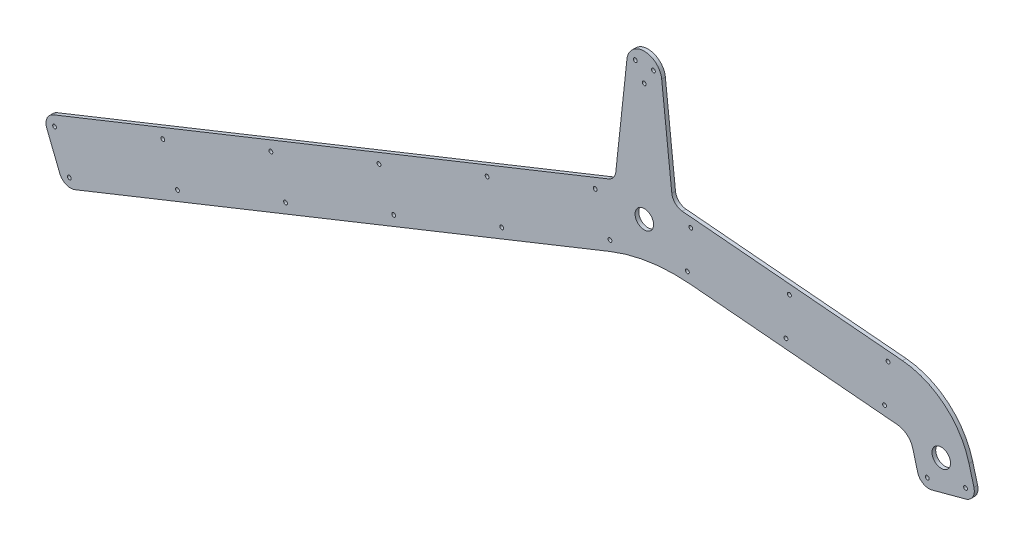
SolidWorks part; units mm, degrees
ref_plane "Front Plane" through (0, 0, 0) normal (0, 0, 1) x (1, 0, 0)
ref_plane "Top Plane" through (0, 0, 0) normal (0, 1, 0) x (1, 0, 0)
ref_plane "Right Plane" through (0, 0, 0) normal (1, 0, 0) x (0, 0, -1)
sketch "Sketch1" plane through (0, 0, 0) normal (0, 0, 1) x (1, 0, 0)
  line L0 (-325, 0) -> (325, 0) construction
  line L1 (-475, -190) -> (-325, 0) construction
  line L2 (325, 0) -> (475, -190) construction
  line L3 (-75, -190) -> (145, -190) construction
  line L4 (145, -190) -> (365, -190) construction
  line L5 (-25.1427, 16.8688) -> (-516.7815, -179.7868)
  line L6 (-516.7815, -179.7868) -> (-498.2119, -226.2106)
  line L7 (-498.2119, -226.2106) -> (-29.4264, -38.6964)
  line L8 (-507.4967, -202.9987) -> (-475, -190) construction
  line L9 (39.3556, -28.5387) -> (217.3643, -44.1124)
  line L11 (221.7221, 5.6973) -> (24.4857, 22.9533)
  line L12 (-25.1427, 16.8688) -> (-6.5731, -29.5551) construction
  line L13 (35, -190) -> (255, -49.8445) construction
  line L14 (255, -49.8445) -> (475, -190) construction
  line L15 (-25.1427, 16.8688) -> (-14.9133, 111.6102)
  line L16 (14.9133, 111.6102) -> (24.4857, 22.9533)
  line L17 (325, 0) -> (325, 80) construction
  line L18 (325, 80) -> (-325, 80) construction
  line L19 (-325, 80) -> (-325, 0) construction
  line L20 (24.4857, 22.9533) -> (20.1279, -26.8565) construction
  line L21 (-15.8579, -6.3432) -> (0, 0) construction
  line L22 (-25.1427, 16.8688) -> (24.4857, 22.9533) construction
  line L23 (230.5459, -55.173) -> (237.3223, -80.4632)
  line L24 (237.3223, -80.4632) -> (285.6186, -67.5222)
  line L25 (285.6186, -67.5222) -> (278.8422, -42.2321)
  line L26 (261.4705, -73.9927) -> (255, -49.8445) construction
  line L29 (0, 0) -> (22.3068, -1.9516) construction
  circle A0 centre (0, 0) radius 7.9375
  circle A1 centre (-475, -190) radius 110 construction
  circle A2 centre (35, -190) radius 110 construction
  circle A3 centre (475, -190) radius 110 construction
  circle A5 centre (255, -49.8445) radius 7.9375
  arc A6 (-14.9133, 111.6102) -> (14.9133, 111.6102) centre (0, 110) cw
  arc A7 (217.3643, -44.1124) -> (230.5459, -55.173) centre (216.057, -59.0553) cw
  arc A8 (221.7221, 5.6973) -> (278.8422, -42.2321) centre (216.057, -59.0553) cw
  arc A9 (-29.4264, -38.6964) -> (39.3556, -28.5387) centre (26.2822, -177.9679) cw
  point P11 (-475, -300)
  point P12 (0, 0)
  point P22 (0, 0)
  point P33 (196.6293, -32.5507)
  dimension "D1" = 15.875
  dimension "D4" = 220
  dimension "D12" = 30
  dimension "D16" = 15
  dimension "D17" = 150
  dimension "D2" = 325
  dimension "D3" = 650
  dimension "D6" = 150
  dimension "D7" = 50
  dimension "D8" = 35
  dimension "D10" = 80
  dimension "D11" = 30
  dimension "D13" = 25
  dimension "D9" = 115
  dimension "D14" = 5
  dimension "D15" = 75
  dimension "D5" = 380
extrude "Base" add sketch "Sketch1" along normal blind 3.175
fillet "Fillet1" radius 10 6 edges at (24.4857, 22.9533, 1.5875) (-25.1427, 16.8688, 1.5875) (237.3223, -80.4632, 1.5875) (285.6186, -67.5222, 1.5875) (-498.2119, -226.2106, 1.5875) (-516.7815, -179.7868, 1.5875)
sketch "Sketch2" plane through (0, 0, 3.175) normal (0, 0, 1) x (1, 0, 0)
  circle A0 centre (0, 110) radius 9 construction
  circle A1 centre (-7.7942, 114.5) radius 1.65
  circle A2 centre (7.7942, 114.5) radius 1.65
  circle A3 centre (0, 101) radius 1.65
  point P5 (22.4231, 127.1589)
  point P6 (0, 0)
  point P11 (0, 110)
  point P12 (-5.4781, 94.0647)
  point P13 (0, 110)
  point P14 (0, 100.9808)
  dimension "D2" = 3.3
  dimension "D3" = 18
  dimension "D1" = 3
extrude "Differential Attachment" cut sketch "Sketch2" against normal through all
sketch "Sketch3" plane through (0, 0, 3.175) normal (0, 0, 1) x (1, 0, 0)
  line L0 (-492.6411, -213.2119) -> (-496.5803, -222.4034) construction
  line L1 (-503.7828, -185.3576) -> (-512.9742, -181.4184) construction
  line L3 (-490.7841, -223.2395) -> (-493.7552, -215.8117) construction
  line L4 (-488.9272, -222.4967) -> (-29.4264, -38.6964) construction
  line L5 (-509.3536, -176.8156) -> (-506.3825, -184.2434) construction
  line L6 (-30.7255, 14.6356) -> (-507.4967, -176.0728) construction
  line L7 (-29.5169, -30.1163) -> (-42.1442, 1.4519) construction
  line L8 (-35.8305, -14.3322) -> (0, 0) construction
  line L9 (0, 0) -> (38.4438, -3.3634) construction
  line L10 (221.7221, 5.6973) -> (32.674, 22.2369) construction
  line L11 (39.9255, 13.5719) -> (36.9622, -20.2987) construction
  line L12 (239.3934, -76.876) -> (244.3934, -68.2157) construction
  line L13 (282.0314, -65.4511) -> (273.3712, -60.4511) construction
  line L14 (242.9792, -70.6652) -> (275.8207, -61.8654) construction
  line L15 (246.9816, -77.875) -> (275.9594, -70.1104) construction
  circle A0 centre (-506.3825, -184.2434) radius 1.65
  circle A1 centre (-493.7552, -215.8117) radius 1.65
  arc A3 (-501.9258, -216.9258) -> (-488.9272, -222.4967) centre (-492.6411, -213.2119) ccw construction
  arc A4 (-507.4967, -176.0728) -> (-513.0675, -189.0715) centre (-503.7828, -185.3576) ccw construction
  circle A5 centre (-400.9076, -178.6726) radius 1.65
  circle A6 centre (-413.5348, -147.1044) radius 1.65
  circle A7 centre (-308.0599, -141.5335) radius 1.65
  circle A8 centre (-320.6872, -109.9653) radius 1.65
  circle A9 centre (-215.2122, -104.3944) radius 1.65
  circle A10 centre (-227.8395, -72.8262) radius 1.65
  circle A11 centre (-122.3646, -67.2554) radius 1.65
  circle A12 centre (-134.9918, -35.6872) radius 1.65
  circle A13 centre (-29.5169, -30.1163) radius 1.65
  circle A14 centre (-42.1442, 1.4519) radius 1.65
  circle A15 centre (39.9255, 13.5719) radius 1.65
  circle A16 centre (36.9622, -20.2987) radius 1.65
  circle A17 centre (124.602, 6.1637) radius 1.65
  circle A18 centre (121.6387, -27.7069) radius 1.65
  circle A19 centre (209.2786, -1.2446) radius 1.65
  circle A20 centre (206.3153, -35.1152) radius 1.65
  circle A21 centre (242.9792, -70.6652) radius 1.65
  circle A22 centre (275.8207, -61.8654) radius 1.65
  arc A23 (234.7341, -70.8039) -> (246.9816, -77.875) centre (244.3934, -68.2157) ccw construction
  arc A24 (275.9594, -70.1104) -> (283.0304, -57.863) centre (273.3712, -60.4511) ccw construction
  point P53 (38.4438, -3.3634)
  point P81 (40.497, 19.4231)
  dimension "D2" = 3.3
  dimension "D1" = 8
  dimension "D5" = 100
  dimension "D6" = 85
  dimension "D3" = 6
  dimension "D4" = 3
extrude "Strut Holes" cut sketch "Sketch3" against normal through all
equation "\"D3@Sketch1\"= \"Chassis Length@Rocker Bogie Assy.Assembly\""
equation "\"D10@Sketch1\"= \"Chassis Height@Rocker Bogie Assy.Assembly\" / 2"
equation "\"D2@Sketch1\"= \"Front to Pivot@Rocker Bogie Assy.Assembly\""
equation "\"D6@Sketch1\"= \"Wheel to Frame@Rocker Bogie Assy.Assembly\""
equation "\"D9@Sketch1\"=\"Bogie Angle@Rocker Bogie Assy.Assembly\""
equation "\"D5@Sketch1\"=\"Chassis Top to Ground@Rocker Bogie Assy.Assembly\""
